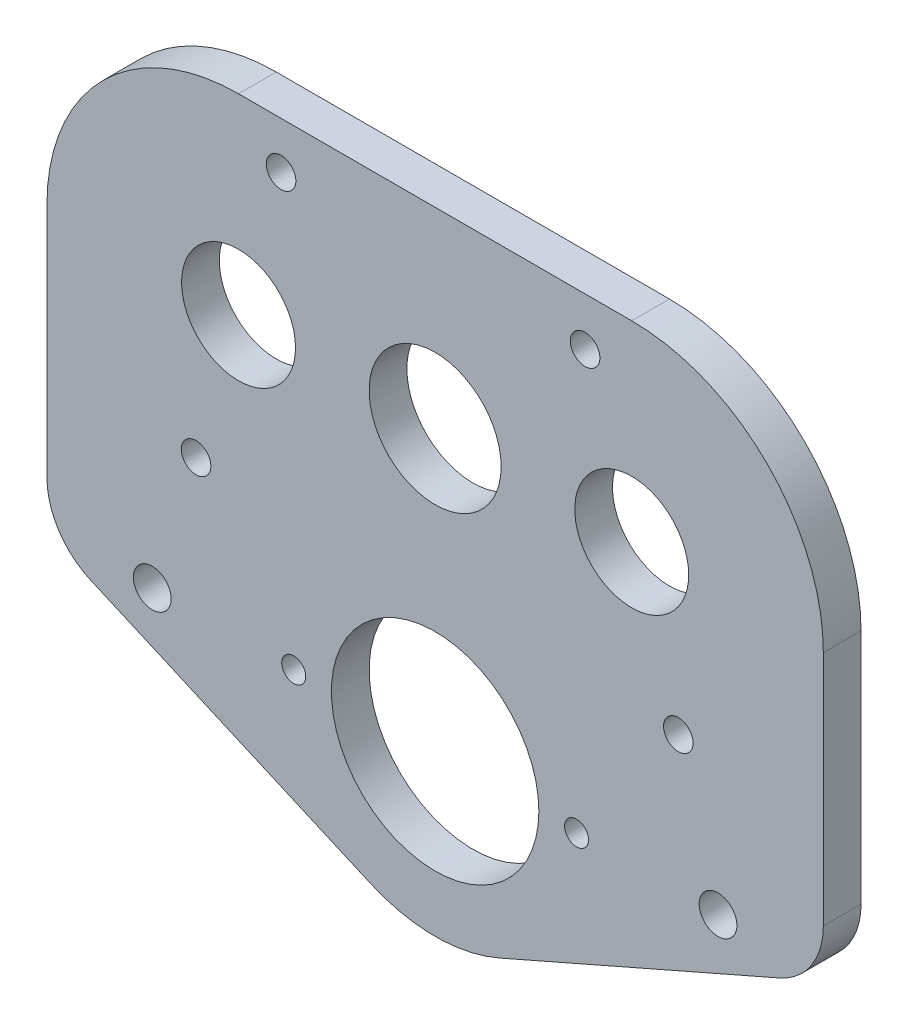
SolidWorks part; units mm, degrees
ref_plane "Front Plane" through (0, 0, 0) normal (0, 0, 1) x (1, 0, 0)
ref_plane "Top Plane" through (0, 0, 0) normal (0, 1, 0) x (1, 0, 0)
ref_plane "Right Plane" through (0, 0, 0) normal (1, 0, 0) x (0, 0, -1)
sketch "Sketch1" plane through (0, 0, 0) normal (0, 0, 1) x (1, 0, 0)
  line L0 (-73.025, -38.1) -> (-73.025, 38.1) construction
  line L1 (-327.025, 38.1) -> (327.025, 38.1) construction
  line L2 (-327.025, 38.1) -> (-327.025, -38.1) construction
  line L3 (-327.025, -38.1) -> (327.025, -38.1) construction
  line L4 (327.025, 38.1) -> (327.025, -38.1) construction
  line L5 (-327.025, 38.1) -> (327.025, -38.1) construction
  line L6 (-327.025, -38.1) -> (327.025, 38.1) construction
  line L7 (-33.0962, 72.4662) -> (-33.0962, 21.6662) construction
  line L8 (-65.3542, 47.0662) -> (-65.3542, 7.2226)
  line L9 (-57.9842, -4.0539) -> (-10.8326, -24.718)
  line L10 (65.3542, 47.0662) -> (65.3542, 7.2223)
  line L11 (57.9842, -4.0542) -> (10.8325, -24.7181)
  line L13 (-33.0962, 79.3242) -> (33.0962, 79.3242)
  line L15 (25.2472, 71.223) -> (40.9452, 22.9094) construction
  line L17 (-40.2522, 22.6951) -> (-25.9402, 71.4373) construction
  circle A0 centre (0, 0) radius 17.4625
  circle A1 centre (0, 0) radius 63.5 construction
  circle A2 centre (47.625, 0) radius 3.175
  circle A3 centre (-23.8125, 0) radius 2.0193
  circle A4 centre (-47.625, 0) radius 3.175
  circle A5 centre (23.8125, 0) radius 2.0193
  circle A6 centre (0, 47.0662) radius 11.1125
  circle A7 centre (33.0962, 47.0662) radius 9.5885
  circle A8 centre (-33.0962, 47.0662) radius 9.5885
  circle A9 centre (-33.0962, 47.0662) radius 32.258 construction
  circle A10 centre (33.0962, 47.0662) radius 32.258 construction
  circle A11 centre (0, 0) radius 26.9875 construction
  circle A12 centre (-47.625, 0) radius 6.35 construction
  circle A13 centre (-33.0962, 21.6662) radius 2.4892 construction
  circle A14 centre (-33.0962, 72.4662) radius 2.4892 construction
  circle A15 centre (33.0962, 21.6662) radius 2.4892 construction
  circle A16 centre (33.0962, 72.4662) radius 2.4892 construction
  circle A17 centre (-25.9402, 71.4373) radius 2.4892
  circle A18 centre (-6.5231, 51.5099) radius 2.4892 [skipped]
  circle A19 centre (-4.4672, 34.1129) radius 2.4892 [skipped]
  circle A20 centre (-11.3852, 18.0188) radius 2.4892 [skipped]
  circle A21 centre (-25.4235, 7.5398) radius 2.4892 [skipped]
  circle A22 centre (-42.8205, 5.4839) radius 2.4892 construction
  circle A23 centre (-19.3639, 68.434) radius 2.4892 construction
  circle A24 centre (-69.3936, 26.4402) radius 2.4892 [skipped]
  circle A25 centre (-71.4495, 43.8372) radius 2.4892 [skipped]
  circle A26 centre (-64.5314, 59.9314) radius 2.4892 [skipped]
  circle A27 centre (-50.4932, 70.4103) radius 2.4892 [skipped]
  circle A28 centre (50.4932, 70.4103) radius 2.4892 [skipped]
  circle A29 centre (64.5314, 59.9314) radius 2.4892 [skipped]
  circle A30 centre (71.4495, 43.8372) radius 2.4892 [skipped]
  circle A31 centre (69.3936, 26.4402) radius 2.4892 [skipped]
  circle A32 centre (-13.9002, 63.6997) radius 2.4892 construction
  circle A33 centre (42.8205, 5.4839) radius 2.4892 construction
  circle A34 centre (25.4235, 7.5398) radius 2.4892 [skipped]
  circle A35 centre (11.3852, 18.0188) radius 2.4892 [skipped]
  circle A36 centre (4.4672, 34.1129) radius 2.4892 [skipped]
  circle A37 centre (6.5231, 51.5099) radius 2.4892 [skipped]
  circle A38 centre (-9.9915, 57.6177) radius 2.4892 construction
  circle A39 centre (0, 47.0662) radius 31.75 construction
  arc A40 (-10.8326, -24.718) -> (10.8325, -24.7181) centre (0, 0) ccw
  arc A41 (-33.0962, 79.3242) -> (-65.3542, 47.0662) centre (-33.0962, 47.0662) ccw
  arc A42 (33.0962, 79.3242) -> (65.3542, 47.0662) centre (33.0962, 47.0662) cw
  arc A43 (65.3542, 7.2223) -> (57.9842, -4.0542) centre (53.0423, 7.2223) cw
  arc A44 (-65.3542, 7.2226) -> (-57.9842, -4.0539) centre (-53.0423, 7.2226) ccw
  circle A45 centre (0, 0) radius 39.37 construction
  circle A46 centre (-17.002, 65.5482) radius 2.4892 construction
  circle A47 centre (-58.9146, 12.4019) radius 2.4892 construction
  circle A48 centre (17.002, 65.5482) radius 2.4892 construction
  circle A49 centre (58.9146, 12.4019) radius 2.4892 [skipped]
  circle A50 centre (-7.9547, 50.681) radius 2.4892 construction
  circle A51 centre (-7.9547, 43.4514) radius 2.4892 construction
  circle A52 centre (-9.9915, 36.5147) radius 2.4892 construction
  circle A53 centre (-13.9002, 30.4327) radius 2.4892 construction
  circle A54 centre (-19.3639, 25.6984) radius 2.4892 construction
  circle A55 centre (-25.9402, 22.6951) radius 2.4892 construction
  circle A56 centre (-33.0962, 21.6662) radius 2.4892 construction
  circle A57 centre (-40.2522, 22.6951) radius 2.4892
  circle A58 centre (-46.8285, 25.6984) radius 2.4892 construction
  circle A59 centre (-52.2922, 30.4327) radius 2.4892 construction
  circle A60 centre (-56.2009, 36.5147) radius 2.4892 construction
  circle A61 centre (-58.2377, 43.4514) radius 2.4892 construction
  circle A62 centre (-58.2377, 50.681) radius 2.4892 construction
  circle A63 centre (-56.2009, 57.6177) radius 2.4892 construction
  circle A64 centre (-52.2922, 63.6997) radius 2.4892 construction
  circle A65 centre (-46.8285, 68.434) radius 2.4892 construction
  circle A66 centre (-40.2522, 71.4373) radius 2.4892 construction
  circle A67 centre (40.9452, 71.223) radius 2.4892 construction
  circle A68 centre (48.0259, 67.6152) radius 2.4892 construction
  circle A69 centre (53.6452, 61.9959) radius 2.4892 construction
  circle A70 centre (57.253, 54.9152) radius 2.4892 construction
  circle A71 centre (58.4962, 47.0662) radius 2.4892 construction
  circle A72 centre (57.253, 39.2172) radius 2.4892 construction
  circle A73 centre (53.6452, 32.1365) radius 2.4892 construction
  circle A74 centre (48.0259, 26.5172) radius 2.4892 construction
  circle A75 centre (40.9452, 22.9094) radius 2.4892
  circle A76 centre (33.0962, 21.6662) radius 2.4892 construction
  circle A77 centre (25.2472, 22.9094) radius 2.4892 construction
  circle A78 centre (18.1665, 26.5172) radius 2.4892 construction
  circle A79 centre (12.5472, 32.1365) radius 2.4892 construction
  circle A80 centre (8.9394, 39.2172) radius 2.4892 construction
  circle A81 centre (7.6962, 47.0662) radius 2.4892 construction
  circle A82 centre (8.9394, 54.9152) radius 2.4892 construction
  circle A83 centre (12.5472, 61.9959) radius 2.4892 construction
  circle A84 centre (18.1665, 67.6152) radius 2.4892 construction
  circle A85 centre (25.2472, 71.223) radius 2.4892
  point P24 (-73.025, -38.1)
  point P62 (-37.9583, 38.9751)
  point P85 (37.9583, 38.9751)
  point P150 (-33.0962, 47.0662)
  point P189 (33.0962, 47.0662)
  dimension "D1" = 34.925
  dimension "D2" = 127
  dimension "D3" = 23.8125
  dimension "D7" = 4.0386
  dimension "D8" = 6.35
  dimension "D9" = 22.225
  dimension "D10" = 19.177
  dimension "D11" = 64.516
  dimension "D16" = 12.7
  dimension "D17" = 4.9784
  dimension "D21" = 63.5
  dimension "D22" = 53.975
  dimension "D24" = 127
  dimension "D27" = 78.74
  dimension "D18" = 50.8
  dimension "D4" = 47.625
  dimension "D5" = 47.625
  dimension "D6" = 23.8125
  dimension "D12" = 33.0962
  dimension "D13" = 33.0962
  dimension "D14" = 47.0662
  dimension "D15" = 254
  dimension "D25" = 50.8
  dimension "D26" = 22
  dimension "D19" = 12
  dimension "D20" = 12
  dimension "D29" = 20
extrude "Boss-Extrude1" add sketch "Sketch1" along normal mid plane 6.35
